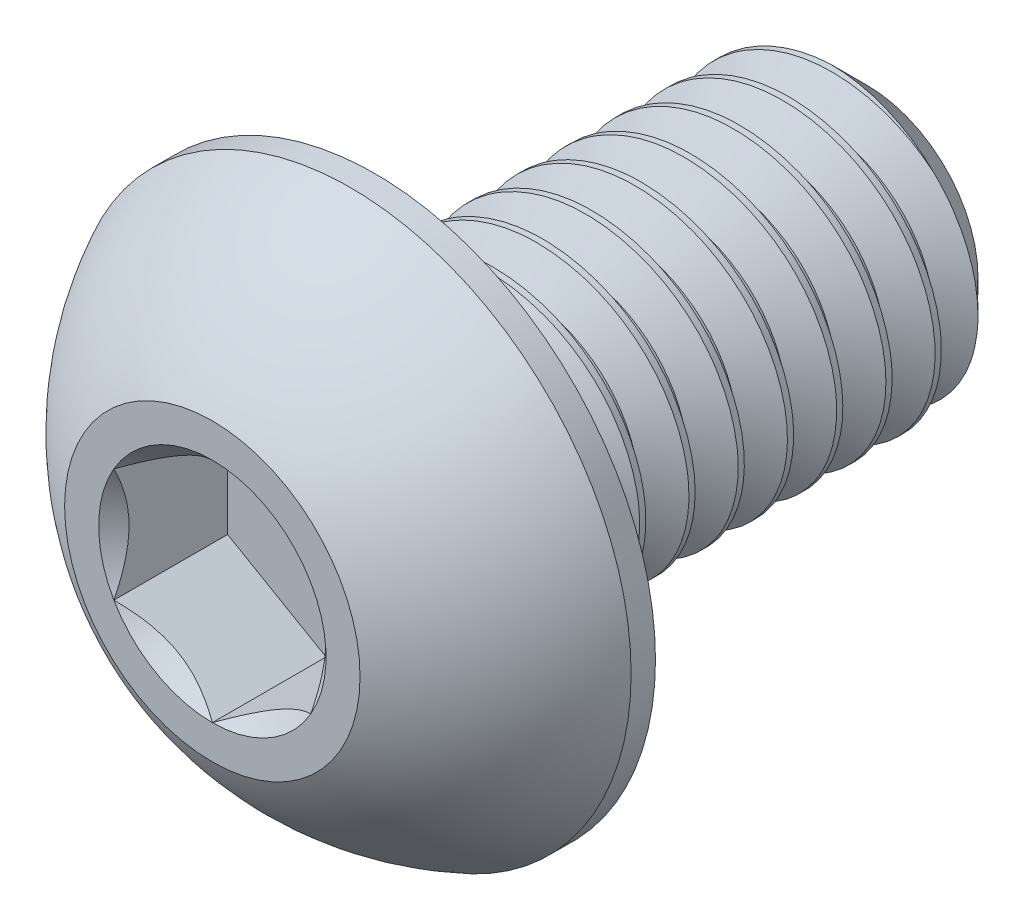
SolidWorks part; units mm, degrees
note: '?' marks a value the reader was unsure of.
ref_plane "Front" through (0, 0, 0) normal (0, 0, 1) x (1, 0, 0)
ref_plane "Top" through (0, 0, 0) normal (0, 1, 0) x (1, 0, 0)
ref_plane "Right" through (0, 0, 0) normal (1, 0, 0) x (0, 0, -1)
sketch "Sketch1" plane through (0, 0, 0) normal (1, 0, 0) x (0, 0, -1)
  line L2 (1.65, 1.5) -> (6.65, 1.5)
  line L3 (6.65, 1.5) -> (6.65, 0)
  line L4 (6.65, 0) -> (1.65, 0)
  line L6 (1.4025, 2.85) -> (1.65, 2.85) construction
  line L7 (6.65, 1.5) -> (6.65, -1.5) construction
  line L8 (0, 0) -> (1.65, 0) construction
  line L9 (1.65, 2.85) -> (1.65, -2.85) construction
  line L11 (1.65, 1.5) -> (1.65, 0)
  line L13 (0, 1) -> (0, -1) construction
  line L14 (0, 1) -> (0, 1.5) construction
  arc A3 (0, 1.5) -> (1.4025, 2.85) centre (2.7948, 0) cw construction
  dimension "D1" = 0.2475
revolve "Revolve1" add sketch "Sketch1" angle 360 mid plane about L4
sketch "Sketch3" plane through (0, 0, -6.65) normal (0, 0, -1) x (-1, 0, 0)
  circle A0 centre (0, 0) radius 1.5
curve "Helix/Spiral1" pitch 0.5 height 5.5 turns 11
chamfer "Chamfer1" distance 0.375 angle 45 1 edges at (0, 1.5, -6.65)
sketch "Sketch7" plane through (0, 0, 0) normal (1, 0, 0) x (0, 0, -1)
  line L6 (1.4025, 2.85) -> (1.65, 2.85) construction
  line L8 (0, 0) -> (1.65, 0) construction
  line L11 (1.65, 2.85) -> (1.65, -2.85) construction
  line L12 (1.4025, 2.85) -> (1.65, 2.85)
  line L13 (0, 0) -> (1.65, 0)
  line L14 (0, 1) -> (0, -1) construction
  line L15 (1.65, 2.85) -> (1.65, 0)
  line L16 (0, 1.5) -> (0, 0)
  arc A2 (1.4025, 2.85) -> (0, 1.5) centre (2.7948, 0) ccw construction
  arc A3 (1.4025, 2.85) -> (0, 1.5) centre (2.7948, 0) ccw
revolve "Revolve2" add sketch "Sketch7" angle 360 mid plane about L13
sketch "Sketch5" plane through (0, 0, 0) normal (0, 0, 1) x (1, 0, 0)
  line L1 (1, -0.5774) -> (1, 0.5774)
  line L2 (1, 0.5774) -> (0, 1.1547)
  line L3 (0, 1.1547) -> (-1, 0.5774)
  line L4 (-1, 0.5774) -> (-1, -0.5774)
  line L5 (-1, -0.5774) -> (0, -1.1547)
  line L6 (0, -1.1547) -> (1, -0.5774)
  circle A0 centre (0, 0) radius 1 construction
extrude "Cut-Extrude2" cut sketch "Sketch5" against normal blind 1.155
sketch "Sketch6" plane through (0, 0, 0) normal (0, 0, 1) x (1, 0, 0)
  circle A0 centre (0, 0) radius 1.1547
extrude "Cut-Extrude3" cut sketch "Sketch6" against normal blind 1.155 draft 45
sketch "Sketch2" plane through (0, 0, 0) normal (1, 0, 0) x (0, 0, -1)
  line L0 (6.275, 1.5) -> (6.7125, 1.5)
  line L1 (6.7125, 1.5) -> (6.525, 1.1752)
  line L2 (6.525, 1.1752) -> (6.4625, 1.1752)
  line L3 (6.4625, 1.1752) -> (6.275, 1.5)
  line L4 (6.3688, 1.3376) -> (6.6188, 1.3376) construction
  dimension "D1" = 60
  dimension "D2" = 0.0625
  dimension "D3" = 0.25
sweep "Cut-Sweep1" cut profiles "Sketch2" path "Helix/Spiral1"
sketch "Sketch10" plane through (0, 0, 0) normal (1, 0, 0) x (0, 0, -1)
  line L0 (6.65, 1.5) -> (6.65, -1.5) construction
  point P0 (5.9, -1.5)
  dimension "D1" = 0.75
ref_axis "Center Axis 1" through (0, 0, -8.1113) along (0, 0, 1)?
ref_plane "Contact Plane 1" through (0, 0, -1.65) normal (0, 0, -1) x (-1, 0, 0)
ref_plane "Contact Plane 2" through (0, 0, 0) normal (0, 0, 1) x (1, 0, 0)
equation "\"D3@Helix/Spiral1\" = \"Lg@Sketch1\" + \"D4@Helix/Spiral1\""
equation "\"D2@Sketch2\" = \"D4@Helix/Spiral1\" * .125"
equation "\"D3@Sketch2\" = \"D4@Helix/Spiral1\" * .5"
equation "\"D1@Chamfer1\" = \"D4@Helix/Spiral1\" * .75"
equation "\"D1@Cut-Extrude2\" = \"Head Ht@Sketch1\" * .7"
equation "\"D1@Sketch1\" = \"Head Ht@Sketch1\" * .15"
equation "\"D1@Sketch10\" = \"D4@Helix/Spiral1\" * 1.5"
equation "\"D1@Cut-Extrude3\" = \"D1@Cut-Extrude2\""
